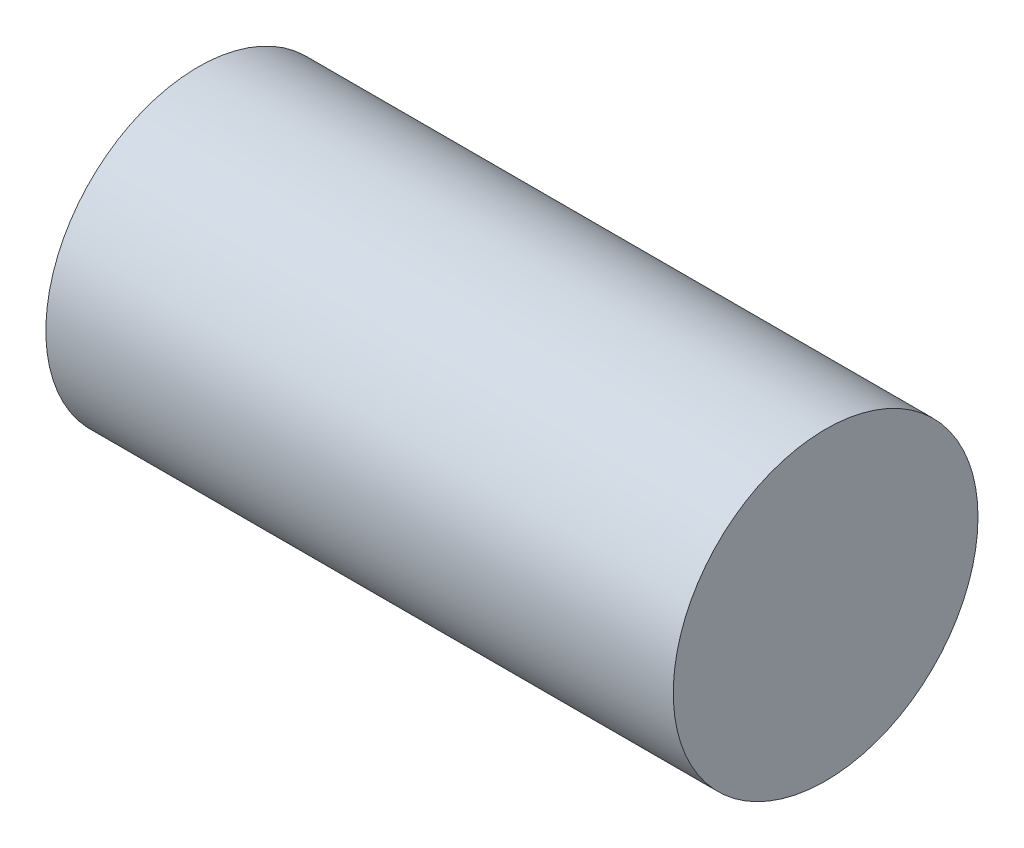
SolidWorks part; units mm, degrees
ref_plane "Front" through (0, 0, 0) normal (0, 0, 1) x (1, 0, 0)
ref_plane "Top" through (0, 0, 0) normal (0, 1, 0) x (1, 0, 0)
ref_plane "Right" through (0, 0, 0) normal (1, 0, 0) x (0, 0, -1)
sketch "Sketch1" plane through (0, 0, 0) normal (1, 0, 0) x (0, 0, -1)
  circle A0 centre (0, 0) radius 8.5
  circle A1 centre (0, 0) radius 8.5 construction
extrude "Boss-Extrude1" add sketch "Sketch1" against normal up to surface (31 mm away)
extrude "Boss-Extrude2" add sketch "Sketch1<2>" along normal blind 2 contours A0
sketch "Sketch1<2>" plane through (0, 0, 0) normal (1, 0, 0) x (0, 0, -1) same geometry as "Sketch1"
sketch "Sketch2" plane through (-31, 0, 0) normal (-1, 0, 0) x (0, 0, 1)
  circle A0 centre (0, 0) radius 8.5
extrude "Boss-Extrude3" add sketch "Sketch2" along normal blind 2
